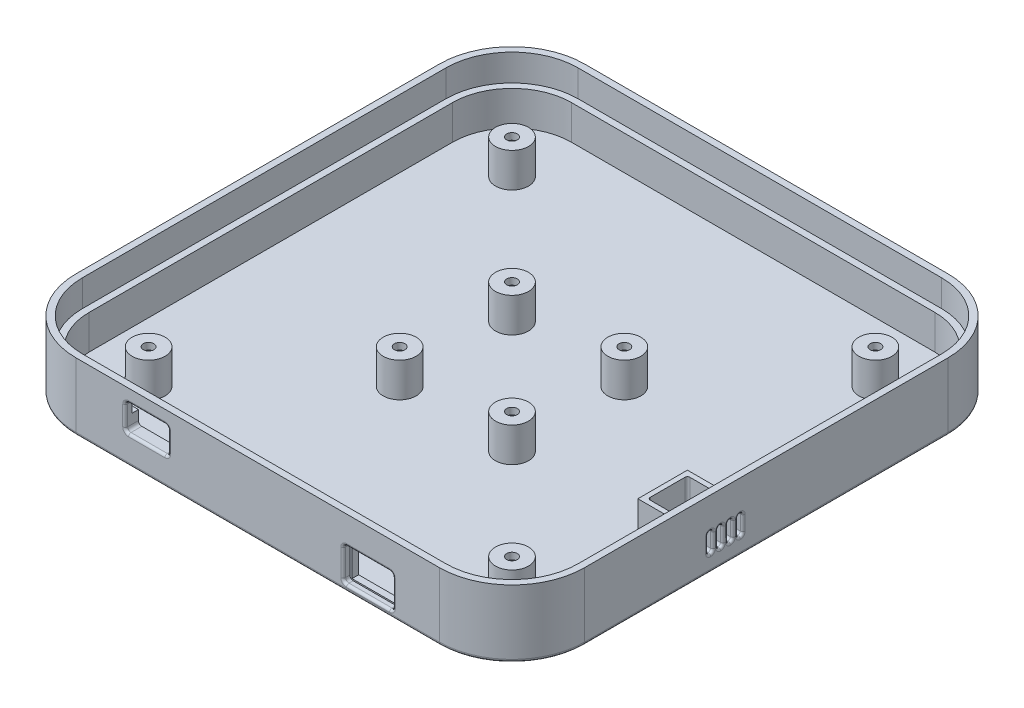
SolidWorks part; units mm, degrees
ref_plane "Front Plane" through (0, 0, 0) normal (0, 0, 1) x (1, 0, 0)
ref_plane "Top Plane" through (0, 0, 0) normal (0, 1, 0) x (1, 0, 0)
ref_plane "Right Plane" through (0, 0, 0) normal (1, 0, 0) x (0, 0, -1)
sketch "Sketch1" plane through (0, 0, 0) normal (0, 1, 0) x (1, 0, 0)
  line L0 (0, 75) -> (55, 75)
  line L1 (75, 55) -> (75, 0)
  line L2 (75, 0) -> (75, -55)
  line L3 (55, -75) -> (0, -75)
  line L4 (0, -75) -> (-55, -75)
  line L5 (-75, -55) -> (-75, 0)
  line L6 (-75, 0) -> (-75, 55)
  line L7 (-55, 75) -> (0, 75)
  line L8 (-55, 77) -> (0, 77)
  line L9 (0, 77) -> (55, 77)
  line L10 (77, 55) -> (77, 0)
  line L11 (77, 0) -> (77, -55)
  line L12 (55, -77) -> (0, -77)
  line L13 (0, -77) -> (-55, -77)
  line L14 (-77, -55) -> (-77, 0)
  line L15 (-77, 0) -> (-77, 55)
  arc A0 (55, 75) -> (75, 55) centre (55, 55) cw
  arc A1 (75, -55) -> (55, -75) centre (55, -55) cw
  arc A2 (-55, -75) -> (-75, -55) centre (-55, -55) cw
  arc A3 (-75, 55) -> (-55, 75) centre (-55, 55) cw
  arc A4 (55, 77) -> (77, 55) centre (55, 55) cw
  arc A5 (77, -55) -> (55, -77) centre (55, -55) cw
  arc A6 (-55, -77) -> (-77, -55) centre (-55, -55) cw
  arc A7 (-77, 55) -> (-55, 77) centre (-55, 55) cw
  point P24 (0, 0)
  dimension "D1" = 75
  dimension "D2" = 75
  dimension "D3" = 20
  dimension "D5" = 2
  dimension "D4" = 4
extrude "Boss-Extrude2" add sketch "Sketch1" along normal blind 18.5
sketch "Sketch4" plane through (0, 0, 0) normal (0, 1, 0) x (1, 0, 0)
  line L20 (55, 73) -> (-55, 73)
  line L21 (73, -55) -> (73, 55)
  line L22 (-55, -73) -> (55, -73)
  line L23 (-73, 55) -> (-73, -55)
  line L24 (55, 73) -> (-55, 73)
  line L25 (73, -55) -> (73, 55)
  line L26 (-55, -73) -> (55, -73)
  line L27 (-73, 55) -> (-73, -55)
  line L44 (55, 75) -> (-55, 75)
  line L45 (75, -55) -> (75, 55)
  line L46 (-55, -75) -> (55, -75)
  line L47 (-75, 55) -> (-75, -55)
  line L48 (55, 75) -> (-55, 75)
  line L49 (75, -55) -> (75, 55)
  line L50 (-55, -75) -> (55, -75)
  line L51 (-75, 55) -> (-75, -55)
  arc A24 (73, 55) -> (55, 73) centre (55, 55) ccw
  arc A25 (55, -73) -> (73, -55) centre (55, -55) ccw
  arc A26 (-73, -55) -> (-55, -73) centre (-55, -55) ccw
  arc A27 (-55, 73) -> (-73, 55) centre (-55, 55) ccw
  arc A28 (73, 55) -> (55, 73) centre (55, 55) ccw
  arc A29 (55, -73) -> (73, -55) centre (55, -55) ccw
  arc A30 (-73, -55) -> (-55, -73) centre (-55, -55) ccw
  arc A31 (-55, 73) -> (-73, 55) centre (-55, 55) ccw
  arc A52 (75, 55) -> (55, 75) centre (55, 55) ccw
  arc A53 (55, -75) -> (75, -55) centre (55, -55) ccw
  arc A54 (-75, -55) -> (-55, -75) centre (-55, -55) ccw
  arc A55 (-55, 75) -> (-75, 55) centre (-55, 55) ccw
  arc A56 (75, 55) -> (55, 75) centre (55, 55) ccw
  arc A57 (55, -75) -> (75, -55) centre (55, -55) ccw
  arc A58 (-75, -55) -> (-55, -75) centre (-55, -55) ccw
  arc A59 (-55, 75) -> (-75, 55) centre (-55, 55) ccw
  dimension "D1" = 2
  dimension "D2" = 0
extrude "Boss-Extrude3" add sketch "Sketch4" along normal blind 10.4
sketch "Sketch5" plane through (0, 0, 0) normal (0, -1, 0) x (1, 0, 0)
  line L8 (-55, -77) -> (55, -77)
  line L9 (77, -55) -> (77, 55)
  line L10 (55, 77) -> (-55, 77)
  line L11 (-77, 55) -> (-77, -55)
  line L12 (-55, -77) -> (55, -77)
  line L13 (77, -55) -> (77, 55)
  line L14 (55, 77) -> (-55, 77)
  line L15 (-77, 55) -> (-77, -55)
  arc A8 (-77, -55) -> (-55, -77) centre (-55, -55) ccw
  arc A9 (55, -77) -> (77, -55) centre (55, -55) ccw
  arc A10 (77, 55) -> (55, 77) centre (55, 55) ccw
  arc A11 (-55, 77) -> (-77, 55) centre (-55, 55) ccw
  arc A12 (-77, -55) -> (-55, -77) centre (-55, -55) ccw
  arc A13 (55, -77) -> (77, -55) centre (55, -55) ccw
  arc A14 (77, 55) -> (55, 77) centre (55, 55) ccw
  arc A15 (-55, 77) -> (-77, 55) centre (-55, 55) ccw
  dimension "D1" = 0
extrude "Boss-Extrude4" add sketch "Sketch5" along normal blind 2
sketch "Sketch6" plane through (0, 0, 77) normal (0, 0, 1) x (1, 0, 0)
  line L0 (-77, 18.5) -> (-77, -2) construction
  line L1 (-40.075, 6.5) -> (-27.075, 6.5)
  line L2 (-40.075, 6.5) -> (-40.075, 14.5)
  line L3 (-40.075, 14.5) -> (-27.075, 14.5)
  line L4 (-27.075, 6.5) -> (-27.075, 14.5)
  line L5 (-40.075, 6.5) -> (-27.075, 14.5) construction
  line L6 (-40.075, 14.5) -> (-27.075, 6.5) construction
  line L7 (55, -2) -> (-55, -2) construction
  point P0 (-33.575, 10.5)
  dimension "D1" = 13
  dimension "D2" = 43.425
  dimension "D3" = 12.5
  dimension "D4" = 8
extrude "Cut-Extrude1" cut sketch "Sketch6" against normal up to next
fillet "Fillet1" radius 1 4 edges at (-40.075, 6.5, 75) (-27.075, 6.5, 75) (-27.075, 14.5, 76) (-40.075, 14.5, 76)
sketch "Sketch7" plane through (77, 0, 0) normal (1, 0, 0) x (0, 0, -1)
  line L0 (-13.15, 8.9478) -> (-13.15, 3.0522)
  line L1 (-17.65, 8.9478) -> (-16.15, 8.9478)
  line L2 (-17.65, 8.9478) -> (-17.65, 3.0522)
  line L3 (-17.65, 3.0522) -> (-16.15, 3.0522)
  line L4 (-16.15, 8.9478) -> (-16.15, 3.0522)
  line L5 (-14.65, 8.9478) -> (-13.15, 8.9478)
  line L6 (-14.65, 8.9478) -> (-14.65, 3.0522)
  line L7 (-14.65, 3.0522) -> (-13.15, 3.0522)
  line L8 (-10.15, 8.9478) -> (-10.15, 3.0522)
  line L9 (-11.65, 8.9478) -> (-10.15, 8.9478)
  line L10 (-11.65, 8.9478) -> (-11.65, 3.0522)
  line L11 (-11.65, 3.0522) -> (-10.15, 3.0522)
  line L12 (-7.15, 8.9478) -> (-7.15, 3.0522)
  line L13 (-8.65, 8.9478) -> (-7.15, 8.9478)
  line L14 (-8.65, 8.9478) -> (-8.65, 3.0522)
  line L15 (-8.65, 3.0522) -> (-7.15, 3.0522)
  line L16 (-13.15, 6) -> (-11.65, 6) construction
  line L17 (-14.65, 6) -> (-16.15, 6) construction
  line L18 (-10.15, 6) -> (-8.65, 6) construction
  line L19 (-77, 18.5) -> (-77, -2) construction
  line L20 (-55, 18.5) -> (55, 18.5) construction
  point P22 (-12.4, 6)
  dimension "D1" = 1.5
  dimension "D3" = 64.6
  dimension "D4" = 12.5
  dimension "D2" = 4
extrude "Cut-Extrude2" cut sketch "Sketch7" against normal up to next
fillet "Fillet3" radius 0.75 8 edges at (-27.3679, 14.2071, 77) (-27.075, 10.5, 77) (-27.3679, 6.7929, 77) (-33.575, 6.5, 77) (-39.7821, 6.7929, 77) (-40.075, 10.5, 77) (-39.7821, 14.2071, 77) (-33.575, 14.5, 77)
fillet "Fillet4" radius 1 8 edges at (70.5563, -2, 70.5563) (77, -2, 0) (70.5563, -2, -70.5563) (0, -2, -77) (-70.5563, -2, -70.5563) (-77, -2, 0) (-70.5563, -2, 70.5563) (0, -2, 77)
sketch "Sketch9" plane through (0, 0, 77) normal (0, 0, 1) x (1, 0, 0)
  line L0 (55, -2) -> (-55, -2) construction
  line L1 (26.9165, 0) -> (39.9165, 0)
  line L2 (25.9165, 1) -> (25.9165, 9)
  line L3 (26.9165, 10) -> (39.9165, 10)
  line L4 (40.9165, 1) -> (40.9165, 9)
  line L5 (25.9165, 0) -> (40.9165, 10) construction
  line L6 (25.9165, 10) -> (40.9165, 0) construction
  arc A0 (39.9165, 10) -> (40.9165, 9) centre (39.9165, 9) cw
  arc A1 (39.9165, 0) -> (40.9165, 1) centre (39.9165, 1) ccw
  arc A2 (26.9165, 0) -> (25.9165, 1) centre (26.9165, 1) cw
  arc A3 (25.9165, 9) -> (26.9165, 10) centre (26.9165, 9) cw
  point P0 (33.4165, 5)
  dimension "D1" = 1
  dimension "D2" = 10
  dimension "D3" = 15
  dimension "D4" = 7
extrude "Cut-Extrude3" cut sketch "Sketch9" against normal blind 2
sketch "Sketch10" plane through (0, 0, 0) normal (0, 1, 0) x (1, 0, 0)
  line L0 (73, -55) -> (73, 55) construction
  line L1 (73, -4.9) -> (58, -4.9)
  line L2 (73, -4.9) -> (73, -6.4)
  line L3 (73, -19.9) -> (58, -19.9)
  line L4 (58, -4.9) -> (58, -19.9)
  line L5 (-55, -77) -> (55, -77) construction
  line L6 (73, -18.4) -> (73, -19.9)
  line L7 (73, -6.4) -> (59.5, -6.4)
  line L9 (73, -18.4) -> (59.5, -18.4)
  line L10 (59.5, -6.4) -> (59.5, -18.4)
  point P7 (58, -12.4)
  dimension "D1" = 15
  dimension "D2" = 15
  dimension "D3" = 64.6
  dimension "D4" = 1.5
  dimension "D5" = 1.5
  dimension "D6" = 1.5
extrude "Boss-Extrude6" add sketch "Sketch10" along normal blind 9.5
fillet "Fillet5" radius 0.75 43 edges at (73, 6, 16.15) (75, 8.9478, 16.15) (77, 6, 16.15) (75, 3.0522, 16.15) (73, 6, 17.65) (75, 3.0522, 17.65) (77, 6, 17.65) (75, 8.9478, 17.65) (73, 6, 14.65) (75, 3.0522, 14.65) (77, 6, 14.65) (75, 8.9478, 14.65) (73, 6, 13.15) (75, 8.9478, 13.15) (77, 6, 13.15) (75, 3.0522, 13.15) (73, 6, 10.15) (75, 8.9478, 10.15) (77, 6, 10.15) (75, 3.0522, 10.15) (73, 6, 11.65) (75, 3.0522, 11.65) (77, 6, 11.65) (75, 8.9478, 11.65) (73, 6, 8.65) (77, 6, 8.65) (75, 8.9478, 8.65) (75, 3.0522, 8.65) (73, 6, 7.15) (75, 8.9478, 7.15) (77, 6, 7.15) (75, 3.0522, 7.15) (73, 4.75, 19.9) (65.5, 0, 19.9) (58, 0, 12.4) (73, 4.75, 4.9) (65.5, 0, 4.9) (59.5, 4.75, 18.4) (59.5, 4.75, 6.4) (59.5, 0, 12.4) (73, 0, 12.4) (66.25, 0, 18.4) (66.25, 0, 6.4)
sketch "Sketch12" plane through (0, 0, 75) normal (0, 0, 1) x (1, 0, 0)
  line L0 (26.9165, 0) -> (39.9165, 0) construction
  line L1 (26.5665, 0.4) -> (40.2665, 0.4)
  line L2 (26.5665, 0.4) -> (26.5665, 9.6)
  line L3 (26.5665, 9.6) -> (40.2665, 9.6)
  line L4 (40.2665, 0.4) -> (40.2665, 9.6)
  line L5 (26.5665, 0.4) -> (40.2665, 9.6) construction
  line L6 (26.5665, 9.6) -> (40.2665, 0.4) construction
  line L7 (40.9165, 1) -> (40.9165, 9) construction
  point P0 (33.4165, 5)
  dimension "D1" = 13.7
  dimension "D2" = 9.2
  dimension "D3" = 5
  dimension "D4" = 7.5
extrude "Cut-Extrude4" cut sketch "Sketch12" against normal up to next
sketch "Sketch14" plane through (0, -2, 0) normal (0, -1, 0) x (1, 0, 0)
  line L0 (-77, -55) -> (-77, 55) construction
  line L1 (-55, 77) -> (55, 77) construction
  line L2 (-76, 0) -> (76, 0) construction
  line L3 (-76, 55) -> (-76, -55) construction
  line L4 (76, -55) -> (76, 55) construction
  circle A0 centre (-55, 55) radius 3
  circle A1 centre (-17, 17) radius 3
  dimension "D1" = 6
  dimension "D4" = 6
  dimension "D2" = 22
  dimension "D3" = 22
  dimension "D5" = 17
  dimension "D6" = 17
extrude "Cut-Extrude5" cut sketch "Sketch14" against normal offset from surface (10.4 mm away) 2 up to face at (-6.715, 10.4, 14.8)
sketch "Sketch15" plane through (0, 0, 0) normal (0, 1, 0) x (1, 0, 0)
  circle A0 centre (-55, -55) radius 3
  circle A1 centre (-55, -55) radius 5
  circle A2 centre (-17, -17) radius 3
  circle A3 centre (-17, -17) radius 5
  dimension "D1" = 2
  dimension "D2" = 2
extrude "Boss-Extrude8" add sketch "Sketch15" along normal offset from surface (8.4 mm away) 2 up to face at (-6.715, 10.4, 14.8)
sketch "Sketch16" plane through (0, 8.4, 0) normal (0, 1, 0) x (1, 0, 0)
  circle A0 centre (-55, -55) radius 5
  circle A1 centre (-55, -55) radius 1.6
  circle A3 centre (-17, -17) radius 1.6
  circle A4 centre (-17, -17) radius 5
  dimension "D1" = 3.2
  dimension "D2" = 3.2
extrude "Boss-Extrude9" add sketch "Sketch16" along normal up to surface (2 mm away) up to face at (-6.715, 10.4, 14.8)
mirror "Mirror1" about plane through (0, 0, 0) normal (0, 0, 1) of "Boss-Extrude8", "Boss-Extrude9", "Cut-Extrude5"
mirror "Mirror2" about plane through (0, 0, 0) normal (1, 0, 0) of "Mirror1"
fillet "Fillet6" radius 0.75 8 edges at (26.2093, 9.7071, 77) (33.4165, 10, 77) (40.6236, 9.7071, 77) (40.9165, 5, 77) (40.6236, 0.2929, 77) (33.4165, 0, 77) (26.2093, 0.2929, 77) (25.9165, 5, 77)
